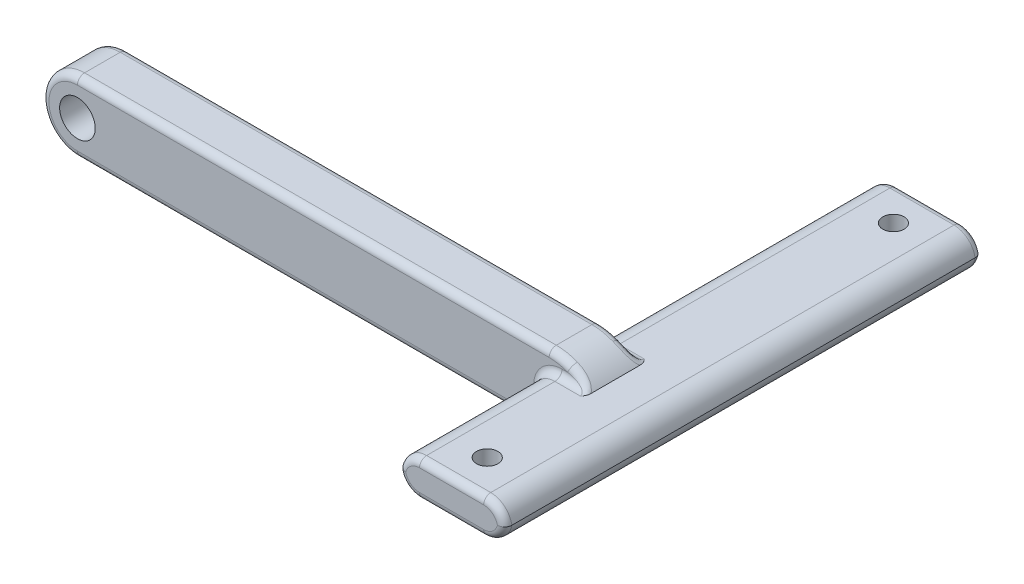
SolidWorks part; units mm, degrees
ref_plane "Plan de face" through (0, 0, 0) normal (0, 0, 1) x (1, 0, 0)
ref_plane "Plan de dessus" through (0, 0, 0) normal (0, 1, 0) x (1, 0, 0)
ref_plane "Plan de droite" through (0, 0, 0) normal (1, 0, 0) x (0, 0, -1)
sketch "Esquisse1" plane through (0, 0, 0) normal (0, 0, 1) x (1, 0, 0)
  line L1 (0, 5) -> (80, 5)
  line L2 (0, 5) -> (0, -5) construction
  line L3 (0, -5) -> (80, -5)
  line L4 (80, 5) -> (80, -5)
  arc A0 (0, 5) -> (0, -5) centre (0, 0) ccw
  circle A1 centre (0, 0) radius 2.5
  dimension "D2" = 5
  dimension "D3" = 80
  dimension "D4" = 10
extrude "Boss.-Extru.1" add sketch "Esquisse1" along normal blind 7
sketch "Esquisse4" plane through (0, 0, 7) normal (0, 0, 1) x (1, 0, 0)
  line L5 (80, -5) -> (80, 5) construction
  line L6 (80, 2.5) -> (65, 2.5)
  line L7 (80, 2.5) -> (80, -2.5)
  line L8 (80, -2.5) -> (65, -2.5)
  line L9 (65, 2.5) -> (65, -2.5)
  line L10 (80, 5) -> (0, 5) construction
  line L11 (0, -5) -> (80, -5) construction
  dimension "D1" = 2.5
  dimension "D2" = 2.5
  dimension "D3" = 15
extrude "Boss.-Extru.3" add sketch "Esquisse4" along normal blind 20
sketch "Esquisse5" plane through (0, 0, 0) normal (0, 0, -1) x (-1, 0, 0)
  line L0 (-80, -5) -> (-80, 5) construction
  line L1 (-80, 2.5) -> (-65, 2.5)
  line L2 (-80, 2.5) -> (-80, -2.5)
  line L3 (-80, -2.5) -> (-65, -2.5)
  line L4 (-65, 2.5) -> (-65, -2.5)
  line L5 (-80, 5) -> (0, 5) construction
  line L6 (0, -5) -> (-80, -5) construction
  dimension "D1" = 2.5
  dimension "D2" = 2.5
  dimension "D3" = 15
extrude "Boss.-Extru.4" add sketch "Esquisse5" along normal blind 40
sketch "Esquisse6" plane through (0, 0, 7) normal (0, 0, 1) x (1, 0, 0)
  line L11 (80, 2.5) -> (65, 2.5) construction
  line L12 (80, 5) -> (72, 5)
  line L13 (80, 5) -> (80, 2.5)
  line L14 (80, 2.5) -> (72, 2.5)
  line L15 (72, 5) -> (72, 2.5)
  line L16 (65, -2.5) -> (80, -2.5) construction
  line L17 (80, -5) -> (72, -5)
  line L18 (80, -5) -> (80, -2.5)
  line L19 (80, -2.5) -> (72, -2.5)
  line L20 (72, -5) -> (72, -2.5)
  dimension "D1" = 8
  dimension "D2" = 8
extrude "Enlèv. mat.-Extru.1" cut sketch "Esquisse6" against normal up to next
sketch "Esquisse7" plane through (0, 2.5, 0) normal (0, 1, 0) x (1, 0, 0)
  line L0 (72.5, 20) -> (72.5, -28) construction
  line L1 (65, 40) -> (80, 40) construction
  line L2 (80, -27) -> (65, -27) construction
  line L3 (80, -27) -> (80, 40) construction
  circle A0 centre (72.5, 35) radius 1.5
  circle A1 centre (72.5, -22) radius 1.5
  dimension "D1" = 3
  dimension "D2" = 3
  dimension "D3" = 5
  dimension "D4" = 5
  dimension "D5" = 7.5
extrude "Enlèv. mat.-Extru.2" cut sketch "Esquisse7" against normal up to next
fillet "Congé1" radius 8 2 edges at (72, 5, 3.5) (72, -5, 3.5)
fillet "Congé2" radius 3 6 edges at (65, -2.5, -20) (65, 2.5, -20) (65, -2.5, 17) (65, 2.5, 17) (80, 2.5, -6.5) (80, -2.5, -6.5)
fillet "Congé3" radius 1 8 edges at (66.0635, 1.7913, 0) (70, 2.5, 0) (66.0635, -1.7913, 0) (70, -2.5, 0) (66.0635, 1.7913, 7) (70, 2.5, 7) (66.0635, -1.7913, 7) (70, -2.5, 7)
fillet "Congé4" radius 1 14 edges at (71.7387, 2.7635, 7.3235) (68.64, -4.6158, 0) (71.7387, -2.7635, -0.3235) (71.8743, 2.6298, -0.5073) (71.8743, -2.6298, 7.5073) (68.64, -4.6158, 7) (-5, 0, 7) (-5, 0, 0) (68.64, 4.6158, 0) (68.64, 4.6158, 7) (33.0953, 5, 0) (33.0953, 5, 7) (33.0953, -5, 0) (33.0953, -5, 7)
fillet "Congé5" radius 1 16 edges at (65.042, 0, -20.5) (65.042, 0, 17.5) (64.8248, 0, -0.3813) (64.8248, 0, 7.3813) (66.0635, -1.7913, -40) (66.0635, 1.7913, -40) (72.5, -2.5, -40) (78.9365, -1.7913, -40) (78.9365, 1.7913, -40) (72.5, 2.5, -40) (72.5, 2.5, 27) (78.9365, 1.7913, 27) (78.9365, -1.7913, 27) (72.5, -2.5, 27) (66.0635, -1.7913, 27) (66.0635, 1.7913, 27)
